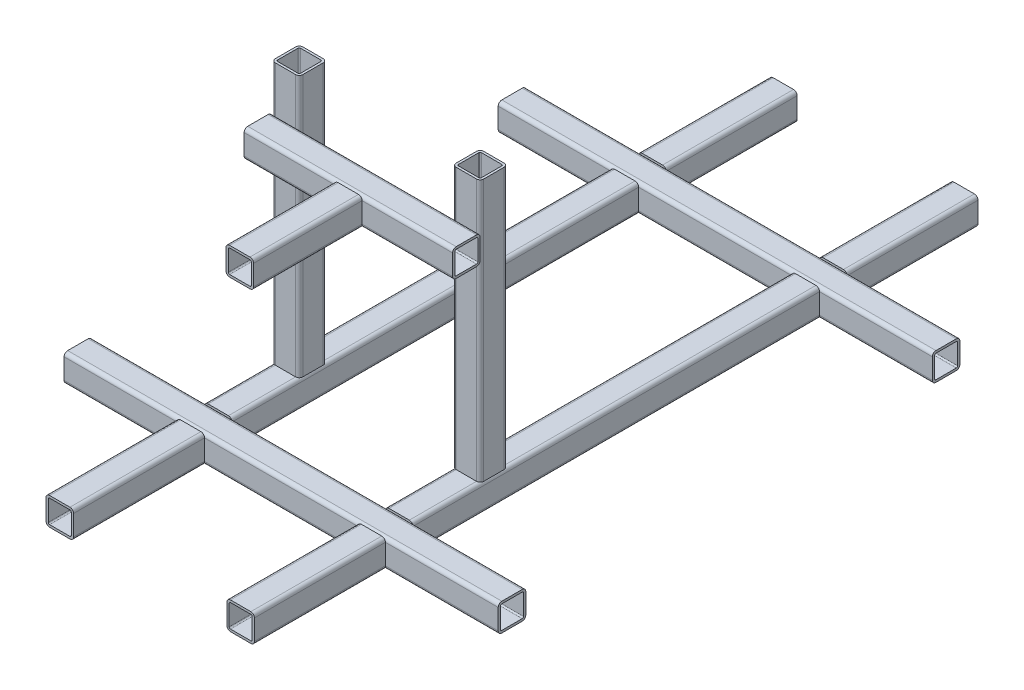
SolidWorks part; units mm, degrees
ref_plane "Front Plane" through (0, 0, 0) normal (0, 0, 1) x (1, 0, 0)
ref_plane "Top Plane" through (0, 0, 0) normal (0, 1, 0) x (1, 0, 0)
ref_plane "Right Plane" through (0, 0, 0) normal (1, 0, 0) x (0, 0, -1)
ref_plane "Bottom Face" through (0, 0, 0) normal (0, 1, 0) x (1, 0, 0)
ref_plane "Top Face" through (0, 38.1, 0) normal (0, 1, 0) x (1, 0, 0)
ref_plane "Mid Plane" through (0, 19.05, 0) normal (0, 1, 0) x (1, 0, 0)
ref_plane "Front Face" through (0, 0, 500) normal (0, 0, 1) x (1, 0, 0)
ref_plane "Back Face" through (0, 0, -500) normal (0, 0, 1) x (1, 0, 0)
ref_plane "Left Face" through (300, 0, 0) normal (1, 0, 0) x (0, 0, -1)
ref_plane "Right Face" through (-300, 0, 0) normal (1, 0, 0) x (0, 0, -1)
ref_plane "Divider Plane" through (0, 0, 150) normal (0, 0, 1) x (1, 0, 0)
ref_plane "Max Height Plane" through (0, 400, 0) normal (0, 1, 0) x (1, 0, 0)
ref_plane "Electronics Box Plane" through (0, 338.1, 0) normal (0, 1, 0) x (1, 0, 0)
sketch "Sketch2" plane through (300, 0, 0) normal (1, 0, 0) x (0, 0, -1)
  line L0 (330, 38.1) -> (-330, 38.1) construction
  line L5 (330, 0) -> (-330, 0) construction
  line L6 (0, 220) -> (0, -220) construction
  line L7 (-314.05, 38.1) -> (-285.95, 38.1)
  line L8 (-280.95, 33.1) -> (-280.95, 5)
  line L9 (-315.875, 33.1) -> (-315.875, 5)
  line L10 (-314.05, 3.175) -> (-285.95, 3.175)
  line L11 (-285.95, 0) -> (-314.05, 0)
  line L12 (-319.05, 5) -> (-319.05, 33.1)
  line L13 (-300, 38.1) -> (-300, 0) construction
  line L14 (-319.05, 19.05) -> (-280.95, 19.05) construction
  line L15 (-284.125, 5) -> (-284.125, 33.1)
  line L16 (-285.95, 34.925) -> (-314.05, 34.925)
  line L17 (-300, 34.925) -> (-300, 3.175) construction
  line L18 (-315.875, 19.05) -> (-284.125, 19.05) construction
  arc A0 (-285.95, 38.1) -> (-280.95, 33.1) centre (-285.95, 33.1) cw
  arc A1 (-280.95, 5) -> (-285.95, 0) centre (-285.95, 5) cw
  arc A2 (-314.05, 0) -> (-319.05, 5) centre (-314.05, 5) cw
  arc A3 (-319.05, 33.1) -> (-314.05, 38.1) centre (-314.05, 33.1) cw
  arc A4 (-315.875, 5) -> (-314.05, 3.175) centre (-314.05, 5) ccw
  arc A5 (-285.95, 3.175) -> (-284.125, 5) centre (-285.95, 5) ccw
  arc A6 (-284.125, 33.1) -> (-285.95, 34.925) centre (-285.95, 33.1) ccw
  arc A7 (-314.05, 34.925) -> (-315.875, 33.1) centre (-314.05, 33.1) ccw
  point P20 (-300, 19.05)
  point P39 (-300, 19.05)
  dimension "D1" = 5
  dimension "D2" = 300
  dimension "D3" = 3.175
extrude "Front Cross-Car Member" add sketch "Sketch2" against normal up to surface (600 mm away) up to plane "Right Face"
sketch "Sketch5" plane through (300, 0, 0) normal (1, 0, 0) x (0, 0, -1)
  line L0 (285.95, 38.1) -> (314.05, 38.1)
  line L1 (319.05, 33.1) -> (319.05, 5)
  line L2 (314.05, 0) -> (285.95, 0)
  line L3 (280.95, 5) -> (280.95, 33.1)
  line L4 (300, 38.1) -> (300, 0) construction
  line L5 (280.95, 19.05) -> (319.05, 19.05) construction
  line L6 (285.95, 34.925) -> (314.05, 34.925)
  line L7 (315.875, 33.1) -> (315.875, 5)
  line L8 (314.05, 3.175) -> (285.95, 3.175)
  line L9 (284.125, 5) -> (284.125, 33.1)
  line L10 (300, 34.925) -> (300, 3.175) construction
  line L11 (284.125, 19.05) -> (315.875, 19.05) construction
  line L12 (330, 0) -> (-330, 0) construction
  line L14 (330, 38.1) -> (-330, 38.1) construction
  line L15 (0, 220) -> (0, -220) construction
  arc A0 (314.05, 38.1) -> (319.05, 33.1) centre (314.05, 33.1) cw
  arc A1 (319.05, 5) -> (314.05, 0) centre (314.05, 5) cw
  arc A2 (285.95, 0) -> (280.95, 5) centre (285.95, 5) cw
  arc A3 (280.95, 33.1) -> (285.95, 38.1) centre (285.95, 33.1) cw
  arc A4 (314.05, 34.925) -> (315.875, 33.1) centre (314.05, 33.1) cw
  arc A5 (315.875, 5) -> (314.05, 3.175) centre (314.05, 5) cw
  arc A6 (285.95, 3.175) -> (284.125, 5) centre (285.95, 5) cw
  arc A7 (284.125, 33.1) -> (285.95, 34.925) centre (285.95, 33.1) cw
  point P32 (300, 19.05)
  point P33 (300, 19.05)
  dimension "D2" = 5
  dimension "D1" = 3.175
  dimension "D3" = 300
extrude "Back Cross-Car Member" add sketch "Sketch5" against normal up to surface (600 mm away) separate body up to plane "Right Face"
sketch "Sketch6" plane through (0, 0, -500) normal (0, 0, 1) x (1, 0, 0)
  line L0 (110.95, 38.1) -> (139.05, 38.1)
  line L1 (144.05, 33.1) -> (144.05, 5)
  line L2 (109.125, 33.1) -> (109.125, 5)
  line L3 (110.95, 3.175) -> (139.05, 3.175)
  line L4 (139.05, 0) -> (110.95, 0)
  line L5 (105.95, 5) -> (105.95, 33.1)
  line L6 (125, 38.1) -> (125, 0) construction
  line L7 (105.95, 19.05) -> (144.05, 19.05) construction
  line L8 (140.875, 5) -> (140.875, 33.1)
  line L9 (139.05, 34.925) -> (110.95, 34.925)
  line L10 (125, 34.925) -> (125, 3.175) construction
  line L11 (109.125, 19.05) -> (140.875, 19.05) construction
  line L12 (330, 38.1) -> (-330, 38.1) construction
  line L13 (330, 0) -> (-330, 0) construction
  line L14 (0, -220) -> (0, 220) construction
  arc A0 (139.05, 38.1) -> (144.05, 33.1) centre (139.05, 33.1) cw
  arc A1 (144.05, 5) -> (139.05, 0) centre (139.05, 5) cw
  arc A2 (110.95, 0) -> (105.95, 5) centre (110.95, 5) cw
  arc A3 (105.95, 33.1) -> (110.95, 38.1) centre (110.95, 33.1) cw
  arc A4 (109.125, 5) -> (110.95, 3.175) centre (110.95, 5) ccw
  arc A5 (139.05, 3.175) -> (140.875, 5) centre (139.05, 5) ccw
  arc A6 (140.875, 33.1) -> (139.05, 34.925) centre (139.05, 33.1) ccw
  arc A7 (110.95, 34.925) -> (109.125, 33.1) centre (110.95, 33.1) ccw
  point P16 (125, 19.05)
  point P33 (125, 19.05)
  dimension "D1" = 5
  dimension "D2" = 3.175
  dimension "D3" = 125
extrude "Back Left Along-Car Member" add sketch "Sketch6" along normal blind 180.95
extrude "Middle Left Along-Car Member" add sketch "Sketch6<2>" along normal blind 561.9 from offset 219.05
sketch "Sketch6<2>" plane through (0, 0, -500) normal (0, 0, 1) x (1, 0, 0) same geometry as "Sketch6"
extrude "Front Left Along-Car Member" add sketch "Sketch6<3>" along normal blind 180.95 from offset 819.05
sketch "Sketch6<3>" plane through (0, 0, -500) normal (0, 0, 1) x (1, 0, 0) same geometry as "Sketch6"
sketch "Sketch7" plane through (0, 0, -500) normal (0, 0, 1) x (1, 0, 0)
  line L0 (-139.05, 38.1) -> (-110.95, 38.1)
  line L1 (-105.95, 33.1) -> (-105.95, 5)
  line L2 (-140.875, 33.1) -> (-140.875, 5)
  line L3 (-139.05, 3.175) -> (-110.95, 3.175)
  line L4 (-110.95, 0) -> (-139.05, 0)
  line L5 (-144.05, 5) -> (-144.05, 33.1)
  line L6 (-125, 38.1) -> (-125, 0) construction
  line L7 (-144.05, 19.05) -> (-105.95, 19.05) construction
  line L8 (-109.125, 5) -> (-109.125, 33.1)
  line L9 (-110.95, 34.925) -> (-139.05, 34.925)
  line L10 (-125, 34.925) -> (-125, 3.175) construction
  line L11 (-140.875, 19.05) -> (-109.125, 19.05) construction
  line L12 (330, 38.1) -> (-330, 38.1) construction
  line L13 (330, 0) -> (-330, 0) construction
  line L14 (0, -220) -> (0, 220) construction
  arc A0 (-110.95, 38.1) -> (-105.95, 33.1) centre (-110.95, 33.1) cw
  arc A1 (-105.95, 5) -> (-110.95, 0) centre (-110.95, 5) cw
  arc A2 (-139.05, 0) -> (-144.05, 5) centre (-139.05, 5) cw
  arc A3 (-144.05, 33.1) -> (-139.05, 38.1) centre (-139.05, 33.1) cw
  arc A4 (-140.875, 5) -> (-139.05, 3.175) centre (-139.05, 5) ccw
  arc A5 (-110.95, 3.175) -> (-109.125, 5) centre (-110.95, 5) ccw
  arc A6 (-109.125, 33.1) -> (-110.95, 34.925) centre (-110.95, 33.1) ccw
  arc A7 (-139.05, 34.925) -> (-140.875, 33.1) centre (-139.05, 33.1) ccw
  point P16 (-125, 19.05)
  point P33 (-125, 19.05)
  dimension "D1" = 5
  dimension "D2" = 3.175
  dimension "D3" = 125
extrude "Back Right Along-Car Member" add sketch "Sketch7" along normal blind 180.95
extrude "Middle Right Along-Car Member" add sketch "Sketch7<2>" along normal blind 561.9 from offset 219.05
sketch "Sketch7<2>" plane through (0, 0, -500) normal (0, 0, 1) x (1, 0, 0) same geometry as "Sketch7"
extrude "Front Right Along-Car Member" add sketch "Sketch7<3>" along normal blind 180.95 from offset 819.05
sketch "Sketch7<3>" plane through (0, 0, -500) normal (0, 0, 1) x (1, 0, 0) same geometry as "Sketch7"
sketch "Sketch8" plane through (0, 38.1, 0) normal (0, 1, 0) x (1, 0, 0)
  line L0 (-139.05, -150) -> (-110.95, -150)
  line L1 (-105.95, -155) -> (-105.95, -183.1)
  line L2 (-140.875, -155) -> (-140.875, -183.1)
  line L3 (-139.05, -184.925) -> (-110.95, -184.925)
  line L4 (-110.95, -188.1) -> (-139.05, -188.1)
  line L5 (-144.05, -183.1) -> (-144.05, -155)
  line L6 (-125, -150) -> (-125, -188.1) construction
  line L7 (-144.05, -169.05) -> (-105.95, -169.05) construction
  line L8 (-109.125, -183.1) -> (-109.125, -155)
  line L9 (-110.95, -153.175) -> (-139.05, -153.175)
  line L10 (-125, -153.175) -> (-125, -184.925) construction
  line L11 (-140.875, -169.05) -> (-109.125, -169.05) construction
  line L12 (-220, -150) -> (220, -150) construction
  line L13 (0, -220) -> (0, 220) construction
  arc A0 (-110.95, -150) -> (-105.95, -155) centre (-110.95, -155) cw
  arc A1 (-105.95, -183.1) -> (-110.95, -188.1) centre (-110.95, -183.1) cw
  arc A2 (-139.05, -188.1) -> (-144.05, -183.1) centre (-139.05, -183.1) cw
  arc A3 (-144.05, -155) -> (-139.05, -150) centre (-139.05, -155) cw
  arc A4 (-140.875, -183.1) -> (-139.05, -184.925) centre (-139.05, -183.1) ccw
  arc A5 (-110.95, -184.925) -> (-109.125, -183.1) centre (-110.95, -183.1) ccw
  arc A6 (-109.125, -155) -> (-110.95, -153.175) centre (-110.95, -155) ccw
  arc A7 (-139.05, -153.175) -> (-140.875, -155) centre (-139.05, -155) ccw
  point P16 (-125, -169.05)
  point P33 (-125, -169.05)
  dimension "D1" = 5
  dimension "D2" = 3.175
  dimension "D3" = 38.1
  dimension "D4" = 125
extrude "Right Vertical Member" add sketch "Sketch8" along normal up to surface (361.9 mm away) up to plane "Max Height Plane"
sketch "Sketch10" plane through (0, 38.1, 0) normal (0, 1, 0) x (1, 0, 0)
  line L0 (110.95, -150) -> (139.05, -150)
  line L1 (144.05, -155) -> (144.05, -183.1)
  line L2 (109.125, -155) -> (109.125, -183.1)
  line L3 (110.95, -184.925) -> (139.05, -184.925)
  line L4 (139.05, -188.1) -> (110.95, -188.1)
  line L5 (105.95, -183.1) -> (105.95, -155)
  line L6 (125, -150) -> (125, -188.1) construction
  line L7 (105.95, -169.05) -> (144.05, -169.05) construction
  line L8 (140.875, -183.1) -> (140.875, -155)
  line L9 (139.05, -153.175) -> (110.95, -153.175)
  line L10 (125, -153.175) -> (125, -184.925) construction
  line L11 (109.125, -169.05) -> (140.875, -169.05) construction
  line L12 (-220, -150) -> (220, -150) construction
  line L13 (0, -220) -> (0, 220) construction
  arc A0 (139.05, -150) -> (144.05, -155) centre (139.05, -155) cw
  arc A1 (144.05, -183.1) -> (139.05, -188.1) centre (139.05, -183.1) cw
  arc A2 (110.95, -188.1) -> (105.95, -183.1) centre (110.95, -183.1) cw
  arc A3 (105.95, -155) -> (110.95, -150) centre (110.95, -155) cw
  arc A4 (109.125, -183.1) -> (110.95, -184.925) centre (110.95, -183.1) ccw
  arc A5 (139.05, -184.925) -> (140.875, -183.1) centre (139.05, -183.1) ccw
  arc A6 (140.875, -155) -> (139.05, -153.175) centre (139.05, -155) ccw
  arc A7 (110.95, -153.175) -> (109.125, -155) centre (110.95, -155) ccw
  point P16 (125, -169.05)
  point P33 (125, -169.05)
  dimension "D1" = 5
  dimension "D2" = 3.175
  dimension "D3" = 38.1
  dimension "D4" = 125
extrude "Left Vertical Member" add sketch "Sketch10" along normal up to surface (361.9 mm away) up to plane "Max Height Plane"
sketch "Sketch11" plane through (300, 0, 0) normal (1, 0, 0) x (0, 0, -1)
  line L0 (-221.2, 338.1) -> (-193.1, 338.1)
  line L1 (-188.1, 333.1) -> (-188.1, 305)
  line L2 (-223.025, 333.1) -> (-223.025, 305)
  line L3 (-221.2, 303.175) -> (-193.1, 303.175)
  line L4 (-193.1, 300) -> (-221.2, 300)
  line L5 (-226.2, 305) -> (-226.2, 333.1)
  line L6 (-207.15, 338.1) -> (-207.15, 300) construction
  line L7 (-226.2, 319.05) -> (-188.1, 319.05) construction
  line L8 (-191.275, 305) -> (-191.275, 333.1)
  line L9 (-193.1, 334.925) -> (-221.2, 334.925)
  line L10 (-207.15, 334.925) -> (-207.15, 303.175) construction
  line L11 (-223.025, 319.05) -> (-191.275, 319.05) construction
  line L12 (-150, 220) -> (-150, -220) construction
  line L13 (330, 338.1) -> (-330, 338.1) construction
  arc A0 (-193.1, 338.1) -> (-188.1, 333.1) centre (-193.1, 333.1) cw
  arc A1 (-188.1, 305) -> (-193.1, 300) centre (-193.1, 305) cw
  arc A2 (-221.2, 300) -> (-226.2, 305) centre (-221.2, 305) cw
  arc A3 (-226.2, 333.1) -> (-221.2, 338.1) centre (-221.2, 333.1) cw
  arc A4 (-223.025, 305) -> (-221.2, 303.175) centre (-221.2, 305) ccw
  arc A5 (-193.1, 303.175) -> (-191.275, 305) centre (-193.1, 305) ccw
  arc A6 (-191.275, 333.1) -> (-193.1, 334.925) centre (-193.1, 333.1) ccw
  arc A7 (-221.2, 334.925) -> (-223.025, 333.1) centre (-221.2, 333.1) ccw
  point P16 (-207.15, 319.05)
  point P33 (-207.15, 319.05)
  dimension "D1" = 5
  dimension "D2" = 3.175
  dimension "D3" = 38.1
  dimension "D4" = 38.1
extrude "Upper Cross-Car Member" add sketch "Sketch11" against normal blind 288.1 from offset 155.95 offset against normal yes
sketch "Sketch12" plane through (0, 0, 150) normal (0, 0, 1) x (1, 0, 0)
  line L0 (-14.05, 338.1) -> (14.05, 338.1)
  line L1 (19.05, 333.1) -> (19.05, 305)
  line L2 (-15.875, 333.1) -> (-15.875, 305)
  line L3 (-14.05, 303.175) -> (14.05, 303.175)
  line L4 (14.05, 300) -> (-14.05, 300)
  line L5 (-19.05, 305) -> (-19.05, 333.1)
  line L6 (0, 338.1) -> (0, 300) construction
  line L7 (-19.05, 319.05) -> (19.05, 319.05) construction
  line L8 (15.875, 305) -> (15.875, 333.1)
  line L9 (14.05, 334.925) -> (-14.05, 334.925)
  line L10 (0, 334.925) -> (0, 303.175) construction
  line L11 (-15.875, 319.05) -> (15.875, 319.05) construction
  line L12 (330, 338.1) -> (-330, 338.1) construction
  line L13 (0, -220) -> (0, 220) construction
  arc A0 (14.05, 338.1) -> (19.05, 333.1) centre (14.05, 333.1) cw
  arc A1 (19.05, 305) -> (14.05, 300) centre (14.05, 305) cw
  arc A2 (-14.05, 300) -> (-19.05, 305) centre (-14.05, 305) cw
  arc A3 (-19.05, 333.1) -> (-14.05, 338.1) centre (-14.05, 333.1) cw
  arc A4 (-15.875, 305) -> (-14.05, 303.175) centre (-14.05, 305) ccw
  arc A5 (14.05, 303.175) -> (15.875, 305) centre (14.05, 305) ccw
  arc A6 (15.875, 333.1) -> (14.05, 334.925) centre (14.05, 333.1) ccw
  arc A7 (-14.05, 334.925) -> (-15.875, 333.1) centre (-14.05, 333.1) ccw
  point P16 (0, 319.05)
  point P33 (0, 319.05)
  dimension "D1" = 5
  dimension "D2" = 3.175
  dimension "D3" = 38.1
extrude "E-Box Platform Base" add sketch "Sketch12" along normal blind 150 from offset 76.2
equation "\"D1@Front Face\" = \"frameLength@Master Assembly.SLDASM\" / 2"
equation "\"D1@Back Face\" = \"frameLength@Master Assembly.SLDASM\" / 2"
equation "\"D1@Left Face\"=\"frameWidth@Master Assembly.SLDASM\"/2"
equation "\"D1@Right Face\" = \"frameWidth@Master Assembly.SLDASM\" / 2"
equation "\"D1@Top Face\"=\"frameTubeStockHeight@Master Assembly.SLDASM\""
equation "\"D2@Sketch2\"=\"frameMemberDistLength@Master Assembly.SLDASM\"/2"
equation "\"D3@Sketch2\"=\"frameTubeStockWallThickness@Master Assembly.SLDASM\""
equation "\"D1@Sketch5\"=\"frameTubeStockWallThickness@Master Assembly.SLDASM\""
equation "\"D3@Sketch5\"=\"frameMemberDistLength@Master Assembly.SLDASM\"/2"
equation "\"D3@Sketch6\"=\"frameMemberDistWidth@Master Assembly.SLDASM\"/2"
equation "\"D1@Back Left Along-Car Member\"=(\"frameLength@Master Assembly.SLDASM\" - \"frameMemberDistLength@Master Assembly.SLDASM\" - \"frameTubeStockHeight@Master Assembly.SLDASM\")  / 2"
equation "\"D19@Middle Left Along-Car Member\" = ( \"frameLength@Master Assembly.SLDASM\" - \"frameMemberDistLength@Master Assembly.SLDASM\" + \"frameTubeStockHeight@Master Assembly.SLDASM\" ) / 2"
equation "\"D1@Middle Left Along-Car Member\"=\"frameMemberDistLength@Master Assembly.SLDASM\" - \"frameTubeStockHeight@Master Assembly.SLDASM\""
equation "\"D19@Front Left Along-Car Member\"=( \"frameLength@Master Assembly.SLDASM\" - \"frameMemberDistLength@Master Assembly.SLDASM\" )  / 2 + \"frameMemberDistLength@Master Assembly.SLDASM\" + \"frameTubeStockHeight@Master Assembly.SLDASM\" / 2"
equation "\"D1@Front Left Along-Car Member\"=(\"frameLength@Master Assembly.SLDASM\" - \"frameMemberDistLength@Master Assembly.SLDASM\" - \"frameTubeStockHeight@Master Assembly.SLDASM\")  / 2"
equation "\"D3@Sketch7\"=\"frameMemberDistWidth@Master Assembly.SLDASM\"/2"
equation "\"D1@Back Right Along-Car Member\"=(\"frameLength@Master Assembly.SLDASM\" - \"frameMemberDistLength@Master Assembly.SLDASM\" - \"frameTubeStockHeight@Master Assembly.SLDASM\")  / 2"
equation "\"D19@Middle Right Along-Car Member\" = ( \"frameLength@Master Assembly.SLDASM\" - \"frameMemberDistLength@Master Assembly.SLDASM\" + \"frameTubeStockHeight@Master Assembly.SLDASM\" ) / 2"
equation "\"D1@Middle Right Along-Car Member\"=\"frameMemberDistLength@Master Assembly.SLDASM\" - \"frameTubeStockHeight@Master Assembly.SLDASM\""
equation "\"D19@Front Right Along-Car Member\"=( \"frameLength@Master Assembly.SLDASM\" - \"frameMemberDistLength@Master Assembly.SLDASM\" )  / 2 + \"frameMemberDistLength@Master Assembly.SLDASM\" + \"frameTubeStockHeight@Master Assembly.SLDASM\" / 2"
equation "\"D1@Front Right Along-Car Member\"=(\"frameLength@Master Assembly.SLDASM\" - \"frameMemberDistLength@Master Assembly.SLDASM\" - \"frameTubeStockHeight@Master Assembly.SLDASM\")  / 2"
equation "\"D1@Divider Plane\"= \"frameDividerPlaneOffset@Master Assembly.SLDASM\""
equation "\"D3@Sketch8\"=\"frameTubeStockHeight@Master Assembly.SLDASM\""
equation "\"D4@Sketch8\"=\"frameMemberDistWidth@Master Assembly.SLDASM\"/2"
equation "\"D1@Max Height Plane\" = \"frameHeight@Master Assembly.SLDASM\""
equation "\"D4@Sketch10\"=\"frameMemberDistWidth@Master Assembly.SLDASM\"/2"
equation "\"D1@Electronics Box Plane\" = \"eboxPlaneHeight@Master Assembly.SLDASM\""
equation "\"D4@Sketch11\"=\"frameTubeStockHeight@Master Assembly.SLDASM\""
equation "\"D19@Upper Cross-Car Member\" = ( \"frameWidth@Master Assembly.SLDASM\" - \"frameMemberDistWidth@Master Assembly.SLDASM\" - \"frameTubeStockHeight@Master Assembly.SLDASM\" ) / 2"
equation "\"D1@Upper Cross-Car Member\" = \"frameMemberDistWidth@Master Assembly.SLDASM\" + \"frameTubeStockHeight@Master Assembly.SLDASM\""
equation "\"D19@E-Box Platform Base\"= \"frameTubeStockHeight@Master Assembly.SLDASM\" * 2"
equation "\"D2@Sketch6\"=\"frameTubeStockWallThickness@Master Assembly.SLDASM\""
equation "\"D2@Sketch7\"=\"frameTubeStockWallThickness@Master Assembly.SLDASM\""
equation "\"D2@Sketch8\"=\"frameTubeStockWallThickness@Master Assembly.SLDASM\""
equation "\"D3@Sketch10\"=\"frameTubeStockHeight@Master Assembly.SLDASM\""
equation "\"D2@Sketch10\"=\"frameTubeStockWallThickness@Master Assembly.SLDASM\""
equation "\"D3@Sketch11\"=\"frameTubeStockHeight@Master Assembly.SLDASM\""
equation "\"D2@Sketch11\"=\"frameTubeStockWallThickness@Master Assembly.SLDASM\""
equation "\"D3@Sketch12\"=\"frameTubeStockHeight@Master Assembly.SLDASM\""
equation "\"D2@Sketch12\"=\"frameTubeStockWallThickness@Master Assembly.SLDASM\""
